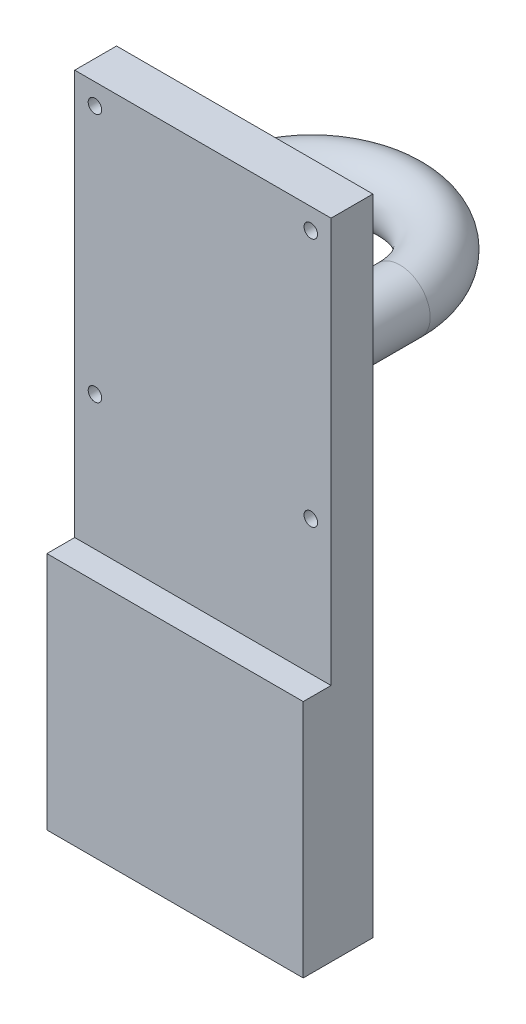
SolidWorks part; units mm, degrees
ref_plane "Plan de face" through (0, 0, 0) normal (0, 0, 1) x (1, 0, 0)
ref_plane "Plan de dessus" through (0, 0, 0) normal (0, 1, 0) x (1, 0, 0)
ref_plane "Plan de droite" through (0, 0, 0) normal (1, 0, 0) x (0, 0, -1)
sketch "Esquisse1" plane through (0, 0, 0) normal (0, 0, 1) x (1, 0, 0)
  line L1 (0, 0) -> (190, 0)
  line L2 (0, 0) -> (0, 300)
  line L3 (0, 300) -> (190, 300)
  line L4 (190, 0) -> (190, 300)
  dimension "D1" = 190
  dimension "D2" = 300
extrude "Boss.-Extru.1" add sketch "Esquisse1" along normal blind 31
sketch "Esquisse2" plane through (0, 0, 0) normal (0, 0, -1) x (-1, 0, 0)
  line L0 (-190, 300) -> (0, 300) construction
  line L3 (-190, 0) -> (-190, 300) construction
  line L4 (0, 300) -> (0, 0) construction
  line L5 (-1232.0432, 99.5) -> (48767.9568, 99.5) construction
  circle A0 centre (-175, 284.5) radius 5
  circle A1 centre (-15, 284.5) radius 5
  circle A2 centre (-175, 99.5) radius 5
  circle A3 centre (-15, 99.5) radius 5
  dimension "D1" = 10
  dimension "D4" = 10
  dimension "D8" = 10
  dimension "D9" = 10
  dimension "D2" = 15.5
  dimension "D3" = 15
  dimension "D5" = 15
  dimension "D6" = 15.5
  dimension "D7" = 200.5
  dimension "D10" = 15
  dimension "D11" = 15
extrude "Enlèv. mat.-Extru.1" cut sketch "Esquisse2" against normal through all
sketch "Esquisse3" plane through (0, 0, 0) normal (0, -1, 0) x (1, 0, 0)
  line L1 (0, 0) -> (190, 0)
  line L2 (0, 0) -> (0, 51.62)
  line L3 (0, 51.62) -> (190, 51.62)
  line L4 (190, 0) -> (190, 51.62)
  dimension "D1" = 190
  dimension "D2" = 51.62
extrude "Boss.-Extru.2" add sketch "Esquisse3" along normal blind 177.45
sketch "Esquisse4" plane through (0, 0, 0) normal (0, 0, -1) x (-1, 0, 0)
  line L0 (-175, 284.5) -> (-15, 99.5) construction
  line L1 (-15, 284.5) -> (-175, 99.5) construction
  line L2 (-1095, 61.275) -> (48905, 61.275) construction
  line L3 (-95, -938.725) -> (-95, 49061.275) construction
  line L4 (-1095, 192) -> (48905, 192) construction
  line L5 (0, 300) -> (0, -177.45) construction
  circle A1 centre (-160, 192) radius 22.5
  circle A2 centre (-30, 192) radius 22.5
  point P19 (-95, 192)
  dimension "D1" = 45
  dimension "D2" = 65
  dimension "D3" = 95
extrude "Boss.-Extru.3" add sketch "Esquisse4" along normal blind 50
sketch "Esquisse5" plane through (0, 0, -50) normal (0, 0, -1) x (-1, 0, 0)
  line L0 (-95, -797.4881) -> (-95, 49202.5119) construction
  line L2 (0, 300) -> (0, -177.45) construction
  line L4 (-190, -177.45) -> (-190, 300) construction
  circle A0 centre (-160, 192) radius 22.5 construction
  circle A1 centre (-160, 192) radius 22.5
  dimension "D1" = 95
  dimension "D2" = 95
revolve "Révolution1" add sketch "Esquisse5" angle 180 about L0
equation "\"D7@Esquisse2\"=216-15.5"
equation "\"D2@Esquisse3\"=31+20.62"
equation "\"D1@Esquisse5\"=190/2"
equation "\"D3@Esquisse4\"=190/2"
